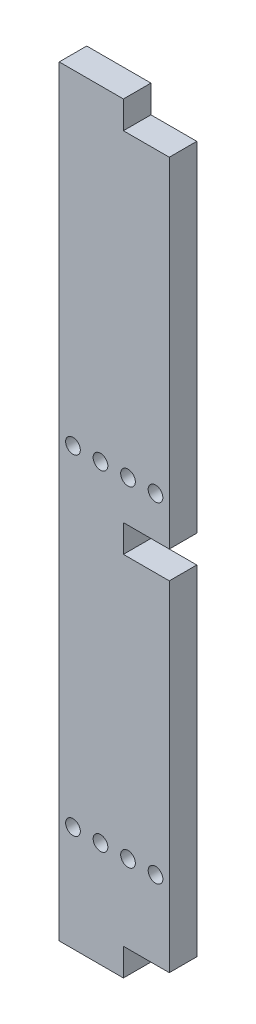
SolidWorks part; units mm, degrees
ref_plane "Plan de face" through (0, 0, 0) normal (0, 0, 1) x (1, 0, 0)
ref_plane "Plan de dessus" through (0, 0, 0) normal (0, 1, 0) x (1, 0, 0)
ref_plane "Plan de droite" through (0, 0, 0) normal (1, 0, 0) x (0, 0, -1)
sketch "Esquisse1" plane through (0, 0, 0) normal (0, 0, 1) x (1, 0, 0)
  line L0 (-6, 0) -> (6, 0)
  line L1 (6, 0) -> (6, 118) construction
  line L2 (6, 118) -> (-6, 118)
  line L3 (-6, 118) -> (-6, 0)
  line L4 (0, 118) -> (0, 0) construction
  line L10 (6, 100.5) -> (1, 100.5)
  line L11 (1, 100.5) -> (1, 97.5)
  line L12 (1, 97.5) -> (6, 97.5)
  line L13 (6, 97.5) -> (6, 60.5)
  line L14 (6, 60.5) -> (1, 60.5)
  line L15 (1, 60.5) -> (1, 57.5)
  line L16 (1, 57.5) -> (6, 57.5)
  line L17 (6, 57.5) -> (6, 20.5)
  line L18 (6, 20.5) -> (1, 20.5)
  line L19 (1, 20.5) -> (1, 17.5)
  line L20 (1, 17.5) -> (6, 17.5)
  line L25 (6, 17.5) -> (6, 0)
  line L26 (1, 99) -> (6, 99) construction
  line L27 (1, 59) -> (6, 59) construction
  line L28 (1, 19) -> (6, 19) construction
  line L32 (3.5, 298) -> (3.5, 99) construction
  line L33 (3.5, 99) -> (3.5, 59) construction
  line L34 (3.5, 59) -> (3.5, 19) construction
  line L35 (3.5, 19) -> (3.5, -180) construction
  line L36 (3.5, 298) -> (3.5, 118) construction
  line L38 (6, 118) -> (6, 100.5)
  point P9 (0, 65)
  point P25 (0, 29)
  point P46 (-0.4418, 19)
  circle B0 centre (0, 105) radius 1.5 construction
  circle B1 centre (0, 93) radius 1.5 construction
  line B2 (-9.0699, 99) -> (8.1862, 99) construction
  circle B3 centre (0, 65) radius 1.5 construction
  circle B4 centre (0, 53) radius 1.5 construction
  line B5 (-9.0699, 59) -> (8.1862, 59) construction
  circle B6 centre (0, 25) radius 1.5 construction
  circle B7 centre (0, 13) radius 1.5 construction
  line B8 (-9.0699, 19) -> (8.1862, 19) construction
  line B9 (-4.5, 65) -> (4.5, 65) construction
  circle B10 centre (-4.5, 65) radius 0.8
  circle B11 centre (-1.5, 65) radius 0.8
  circle B12 centre (1.5, 65) radius 0.8
  circle B13 centre (4.5, 65) radius 0.8
  line B14 (-4.5, 29) -> (4.5, 29) construction
  circle B15 centre (-4.5, 29) radius 0.8
  circle B16 centre (-1.5, 29) radius 0.8
  circle B17 centre (1.5, 29) radius 0.8
  circle B18 centre (4.5, 29) radius 0.8
  dimension "D6" = 6
  dimension "D1" = 40
  dimension "D2" = 17.5
  dimension "D3" = 3
  dimension "D4" = 12
  dimension "D5" = 5
  dimension "10" = 10
sketch_block_instance "Bloc1-2"
sketch_block "Bloc1" parameters "D1"=3, "D3"=3, "D2"=12
sketch_block_instance "Bloc1-3"
sketch_block_instance "Bloc1-5"
sketch_block_instance "Bloc2-2"
sketch_block "Bloc2" parameters "D4"=1.6, "D1"=3, "D2"=3, "D3"=3, "D5"=9
sketch_block_instance "Bloc2-3"
extrude "Boss.-Extru.1" add sketch "Esquisse1" along normal blind 3
sketch "Esquisse2" plane through (0, 0, 3) normal (0, 0, 1) x (1, 0, 0)
  line L1 (-6, 118) -> (6, 118)
  line L2 (-6, 118) -> (-6, 100.5)
  line L3 (-6, 100.5) -> (6, 100.5)
  line L4 (6, 118) -> (6, 100.5)
  line L5 (-6, 0) -> (6, 0)
  line L6 (-6, 0) -> (-6, 17.5)
  line L7 (-6, 17.5) -> (6, 17.5)
  line L8 (6, 0) -> (6, 17.5)
extrude "Enlèv. mat.-Extru.1" cut sketch "Esquisse2" against normal through all
